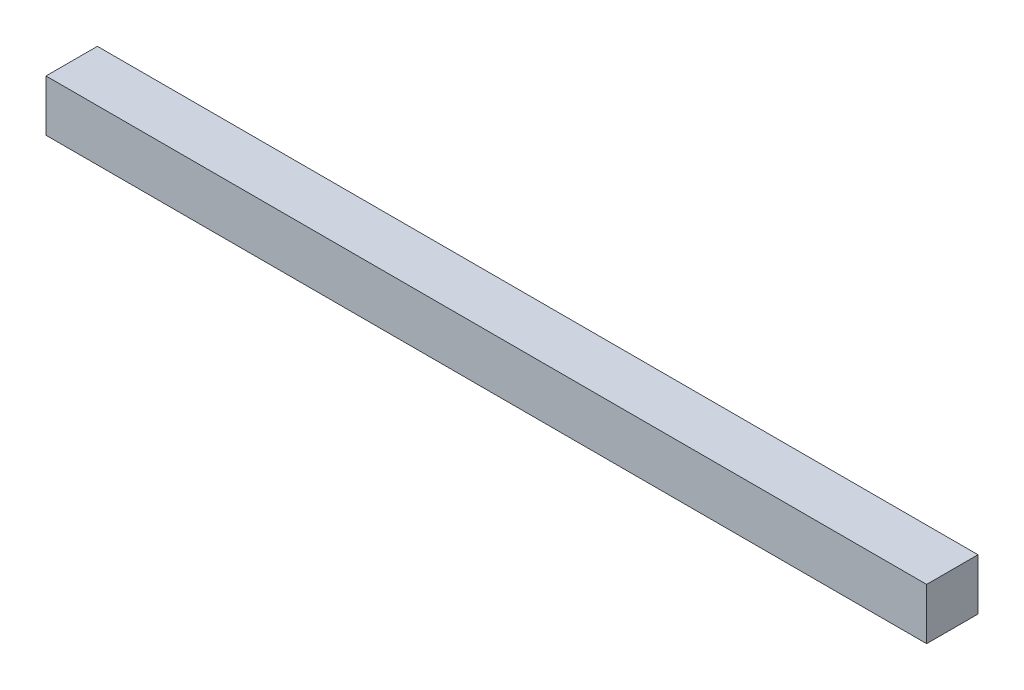
SolidWorks part; units mm, degrees
ref_plane "Front Plane" through (0, 0, 0) normal (0, 0, 1) x (1, 0, 0)
ref_plane "Top Plane" through (0, 0, 0) normal (0, 1, 0) x (1, 0, 0)
ref_plane "Right Plane" through (0, 0, 0) normal (1, 0, 0) x (0, 0, -1)
sketch "Sketch1" plane through (0, 0, 0) normal (1, 0, 0) x (0, 0, -1)
  line L1 (-22.225, 22.225) -> (22.225, 22.225)
  line L2 (-22.225, 22.225) -> (-22.225, -22.225)
  line L3 (-22.225, -22.225) -> (22.225, -22.225)
  line L4 (22.225, 22.225) -> (22.225, -22.225)
  line L5 (-22.225, 22.225) -> (22.225, -22.225) construction
  line L6 (-22.225, -22.225) -> (22.225, 22.225) construction
  point P0 (0, 0)
  dimension "D1" = 44.45
  dimension "D2" = 44.45
extrude "Boss-Extrude1" add sketch "Sketch1" along normal blind 381 and the other way blind 381
